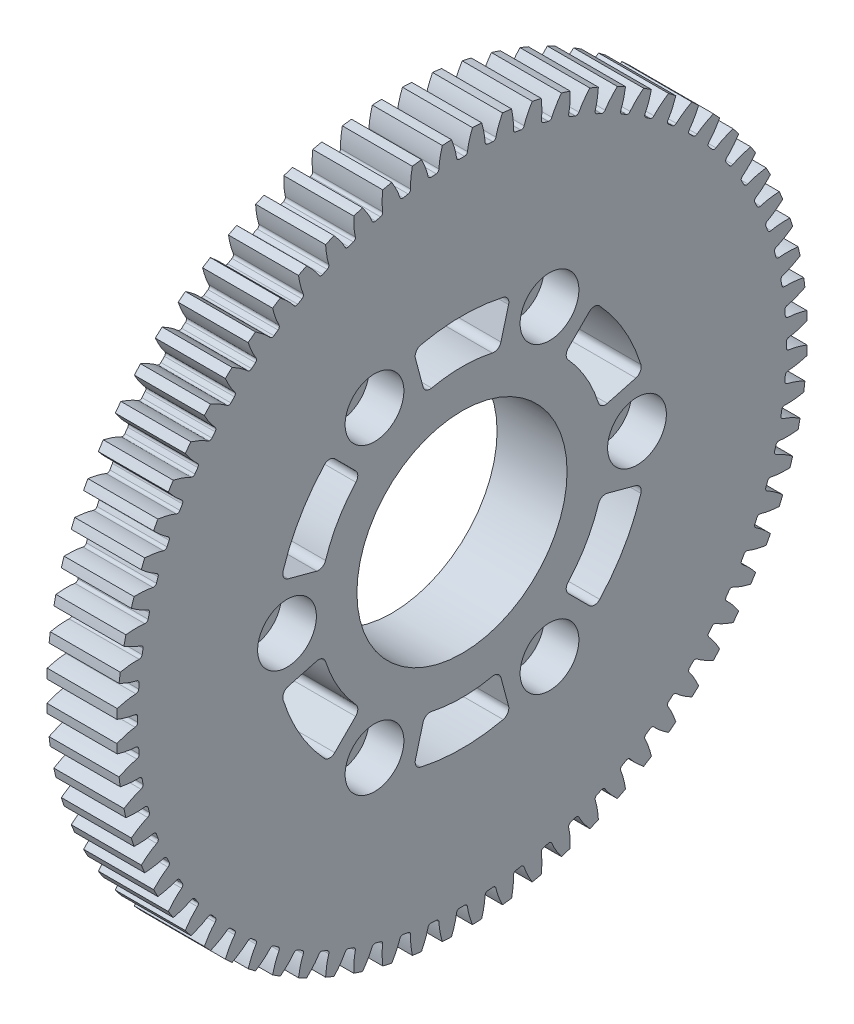
SolidWorks part; units mm, degrees
material "7075-T6 (SN)"
ref_plane "Front Plane" through (0, 0, 0) normal (0, 0, 1) x (1, 0, 0)
ref_plane "Top Plane" through (0, 0, 0) normal (0, 1, 0) x (1, 0, 0)
ref_plane "Right Plane" through (0, 0, 0) normal (1, 0, 0) x (0, 0, -1)
ref_axis "Axis1" through (-8.8445, 0, 0) along (1, 0, 0)
sketch "Sketch1" plane through (0, 0, 0) normal (1, 0, 0) x (0, 0, -1)
  circle A0 centre (0, 0) radius 46.99
  dimension "D1" = 93.98
extrude "Boss-Extrude1" add sketch "Sketch1" along normal mid plane 9.525
sketch "Sketch2" plane through (0, 0, 0) normal (1, 0, 0) x (0, 0, -1)
  line L0 (44.2579, 0.7202) -> (44.1267, 0.7181)
  line L1 (44.2579, -0.7202) -> (44.1267, -0.7181)
  circle A0 centre (0, 0) radius 46.99 construction
  circle A1 centre (0, 0) radius 45.72 construction
  circle A2 centre (0, 0) radius 44.2637 construction
  circle A3 centre (0, 0) radius 44.1325 construction
  circle A4 centre (0, 0) radius 46.99 construction
  arc A5 (44.1267, 0.7181) -> (44.1267, -0.7181) centre (0, 0) cw
  arc A6 (46.9684, 1.4236) -> (46.9684, -1.4236) centre (0, 0) cw
  spline S0 degree 4 poles (44.2579, 0.7202) (44.262, 0.7203) (44.2737, 0.7207) (44.2957, 0.7218) (44.3316, 0.7241) (44.3774, 0.7279) (44.4367, 0.7337) (44.5065, 0.7417) (44.5833, 0.7517) (44.667, 0.764) (44.7505, 0.7774) (44.8338, 0.792) (44.917, 0.8074) (45.0177, 0.8274) (45.1387, 0.853) (45.2803, 0.8853) (45.4412, 0.9248) (45.6054, 0.9682) (45.7673, 1.0134) (45.9313, 1.062) (46.0901, 1.1111) (46.2555, 1.1652) (46.4084, 1.2166) (46.5801, 1.2776) (46.7189, 1.3278) (46.9024, 1.3977) (47.0109, 1.44) (47.1382, 1.4908) (47.1948, 1.514) (47.2297, 1.5283) knots 0 0 0 0 0 0.005377 0.015084 0.028532 0.04661 0.064855 0.092111 0.119476 0.146842 0.174209 0.201575 0.228941 0.256307 0.307035 0.361767 0.4165 0.471232 0.525964 0.580697 0.635429 0.690161 0.744894 0.799626 0.854358 0.909091 0.954545 1 1 1 1 1 construction
  spline S1 degree 4 poles (44.2579, 0.7202) (44.262, 0.7203) (44.2737, 0.7207) (44.2957, 0.7218) (44.3316, 0.7241) (44.3774, 0.7279) (44.4367, 0.7337) (44.5065, 0.7417) (44.5833, 0.7517) (44.667, 0.764) (44.7505, 0.7774) (44.8338, 0.792) (44.917, 0.8074) (45.0177, 0.8274) (45.1387, 0.853) (45.2803, 0.8853) (45.4412, 0.9248) (45.6054, 0.9682) (45.7673, 1.0134) (45.9313, 1.062) (46.0901, 1.1111) (46.2555, 1.1652) (46.4084, 1.2166) (46.5801, 1.2776) (46.7189, 1.3278) (46.8626, 1.3825) (46.9326, 1.4096) (46.9684, 1.4236) knots 0 0 0 0 0 0.005377 0.015084 0.028532 0.04661 0.064855 0.092111 0.119476 0.146842 0.174209 0.201575 0.228941 0.256307 0.307035 0.361767 0.4165 0.471232 0.525964 0.580697 0.635429 0.690161 0.744894 0.799626 0.854358 0.909091 0.909091 0.909091 0.909091 0.909091
  spline S2 degree 4 poles (44.2579, -0.7202) (44.262, -0.7203) (44.2737, -0.7207) (44.2957, -0.7218) (44.3316, -0.7241) (44.3774, -0.7279) (44.4367, -0.7337) (44.5065, -0.7417) (44.5833, -0.7517) (44.667, -0.764) (44.7505, -0.7774) (44.8338, -0.792) (44.917, -0.8074) (45.0177, -0.8274) (45.1387, -0.853) (45.2803, -0.8853) (45.4412, -0.9248) (45.6054, -0.9682) (45.7673, -1.0134) (45.9313, -1.062) (46.0901, -1.1111) (46.2555, -1.1652) (46.4084, -1.2166) (46.5801, -1.2776) (46.7189, -1.3278) (46.9024, -1.3977) (47.0109, -1.44) (47.1382, -1.4908) (47.1948, -1.514) (47.2297, -1.5283) knots 0 0 0 0 0 0.005377 0.015084 0.028532 0.04661 0.064855 0.092111 0.119476 0.146842 0.174209 0.201575 0.228941 0.256307 0.307035 0.361767 0.4165 0.471232 0.525964 0.580697 0.635429 0.690161 0.744894 0.799626 0.854358 0.909091 0.954545 1 1 1 1 1 construction
  spline S3 degree 4 poles (44.2579, -0.7202) (44.262, -0.7203) (44.2737, -0.7207) (44.2957, -0.7218) (44.3316, -0.7241) (44.3774, -0.7279) (44.4367, -0.7337) (44.5065, -0.7417) (44.5833, -0.7517) (44.667, -0.764) (44.7505, -0.7774) (44.8338, -0.792) (44.917, -0.8074) (45.0177, -0.8274) (45.1387, -0.853) (45.2803, -0.8853) (45.4412, -0.9248) (45.6054, -0.9682) (45.7673, -1.0134) (45.9313, -1.062) (46.0901, -1.1111) (46.2555, -1.1652) (46.4084, -1.2166) (46.5801, -1.2776) (46.7189, -1.3278) (46.8626, -1.3825) (46.9326, -1.4096) (46.9684, -1.4236) knots 0 0 0 0 0 0.005377 0.015084 0.028532 0.04661 0.064855 0.092111 0.119476 0.146842 0.174209 0.201575 0.228941 0.256307 0.307035 0.361767 0.4165 0.471232 0.525964 0.580697 0.635429 0.690161 0.744894 0.799626 0.854358 0.909091 0.909091 0.909091 0.909091 0.909091
  dimension "D1" = 93.98
  dimension "D2" = 91.44
  dimension "D3" = 88.5274
  dimension "D4" = 88.265
extrude "Cut-Extrude1" cut sketch "Sketch2" against normal through all both and the other way through all
fillet "Fillet1" radius 0.397 2 edges at (0, -0.7181, -44.1267) (0, 0.7181, -44.1267)
pattern_circular "CirPattern1" count 72 over 360 about axis through (4.7625, 0, 0) along (-1, 0, 0) of "Cut-Extrude1", "Fillet1" reverse direction yes
sketch "Sketch5" [suppressed] plane through (0, 0, 0) normal (1, 0, 0) x (0, 0, -1)
  circle A0 centre (0, 0) radius 51.641 construction
  circle A1 centre (0, 0) radius 51.7525 construction
  circle A2 centre (0, 0) radius 53.34 construction
  circle A3 centre (0, 0) radius 54.61 construction
  arc A4 (51.6365, 0.6793) -> (51.6365, -0.6793) centre (0, 0) cw
  arc A5 (54.5918, 1.4103) -> (54.5918, -1.4103) centre (0, 0) cw
  spline S0 degree 4 poles (51.6365, 0.6793) (51.641, 0.6794) (51.6537, 0.6798) (51.6776, 0.6809) (51.7167, 0.6832) (51.7665, 0.687) (51.831, 0.6929) (51.9069, 0.7011) (51.9905, 0.7115) (52.0815, 0.7241) (52.1723, 0.738) (52.2631, 0.753) (52.3536, 0.769) (52.4633, 0.7897) (52.5951, 0.8162) (52.7493, 0.8497) (52.9246, 0.8907) (53.1037, 0.9358) (53.2802, 0.9828) (53.459, 1.0334) (53.6324, 1.0846) (53.8129, 1.1409) (53.9798, 1.1945) (54.1674, 1.2581) (54.319, 1.3104) (54.5196, 1.3833) (54.6383, 1.4275) (54.7774, 1.4805) (54.8393, 1.5048) (54.8775, 1.5197) knots 0 0 0 0 0 0.005377 0.015084 0.028532 0.04661 0.064855 0.092111 0.119476 0.146842 0.174209 0.201575 0.228941 0.256307 0.307035 0.361767 0.4165 0.471232 0.525964 0.580697 0.635429 0.690161 0.744894 0.799626 0.854358 0.909091 0.954545 1 1 1 1 1 construction
  spline S1 degree 4 poles (51.6365, 0.6793) (51.641, 0.6794) (51.6537, 0.6798) (51.6776, 0.6809) (51.7167, 0.6832) (51.7665, 0.687) (51.831, 0.6929) (51.9069, 0.7011) (51.9905, 0.7115) (52.0815, 0.7241) (52.1723, 0.738) (52.2631, 0.753) (52.3536, 0.769) (52.4633, 0.7897) (52.5951, 0.8162) (52.7493, 0.8497) (52.9246, 0.8907) (53.1037, 0.9358) (53.2802, 0.9828) (53.459, 1.0334) (53.6324, 1.0846) (53.8129, 1.1409) (53.9798, 1.1945) (54.1674, 1.2581) (54.319, 1.3104) (54.4761, 1.3675) (54.5526, 1.3957) (54.5918, 1.4103) knots 0 0 0 0 0 0.005377 0.015084 0.028532 0.04661 0.064855 0.092111 0.119476 0.146842 0.174209 0.201575 0.228941 0.256307 0.307035 0.361767 0.4165 0.471232 0.525964 0.580697 0.635429 0.690161 0.744894 0.799626 0.854358 0.909091 0.909091 0.909091 0.909091 0.909091
  spline S2 degree 4 poles (51.6365, -0.6793) (51.641, -0.6794) (51.6537, -0.6798) (51.6776, -0.6809) (51.7167, -0.6832) (51.7665, -0.687) (51.831, -0.6929) (51.9069, -0.7011) (51.9905, -0.7115) (52.0815, -0.7241) (52.1723, -0.738) (52.2631, -0.753) (52.3536, -0.769) (52.4633, -0.7897) (52.5951, -0.8162) (52.7493, -0.8497) (52.9246, -0.8907) (53.1037, -0.9358) (53.2802, -0.9828) (53.459, -1.0334) (53.6324, -1.0846) (53.8129, -1.1409) (53.9798, -1.1945) (54.1674, -1.2581) (54.319, -1.3104) (54.5196, -1.3833) (54.6383, -1.4275) (54.7774, -1.4805) (54.8393, -1.5048) (54.8775, -1.5197) knots 0 0 0 0 0 0.005377 0.015084 0.028532 0.04661 0.064855 0.092111 0.119476 0.146842 0.174209 0.201575 0.228941 0.256307 0.307035 0.361767 0.4165 0.471232 0.525964 0.580697 0.635429 0.690161 0.744894 0.799626 0.854358 0.909091 0.954545 1 1 1 1 1 construction
  spline S3 degree 4 poles (51.6365, -0.6793) (51.641, -0.6794) (51.6537, -0.6798) (51.6776, -0.6809) (51.7167, -0.6832) (51.7665, -0.687) (51.831, -0.6929) (51.9069, -0.7011) (51.9905, -0.7115) (52.0815, -0.7241) (52.1723, -0.738) (52.2631, -0.753) (52.3536, -0.769) (52.4633, -0.7897) (52.5951, -0.8162) (52.7493, -0.8497) (52.9246, -0.8907) (53.1037, -0.9358) (53.2802, -0.9828) (53.459, -1.0334) (53.6324, -1.0846) (53.8129, -1.1409) (53.9798, -1.1945) (54.1674, -1.2581) (54.319, -1.3104) (54.4761, -1.3675) (54.5526, -1.3957) (54.5918, -1.4103) knots 0 0 0 0 0 0.005377 0.015084 0.028532 0.04661 0.064855 0.092111 0.119476 0.146842 0.174209 0.201575 0.228941 0.256307 0.307035 0.361767 0.4165 0.471232 0.525964 0.580697 0.635429 0.690161 0.744894 0.799626 0.854358 0.909091 0.909091 0.909091 0.909091 0.909091
  dimension "D1" = 88.265
  dimension "D2" = 88.5274
  dimension "D3" = 91.44
  dimension "D4" = 93.98
extrude "Cut-Extrude2" [suppressed] cut sketch "Sketch5" against normal through all both and the other way through all
fillet "Fillet2" [suppressed] radius 0.397
pattern_circular "CirPattern2" [suppressed] count 84 over 360 of bodies 108
sketch "Sketch6" plane through (0, 0, 0) normal (1, 0, 0) x (0, 0, -1)
  line L0 (-6.5999, 24.6311) -> (-5.047, 18.8356)
  line L1 (23.8125, 0) -> (11.9062, 20.6222) construction
  line L2 (11.9062, 20.6222) -> (-11.9063, 20.6222) construction
  line L3 (-11.9063, 20.6222) -> (-23.8125, 0) construction
  line L4 (-23.8125, 0) -> (-11.9063, -20.6222) construction
  line L5 (-11.9063, -20.6222) -> (11.9062, -20.6222) construction
  line L6 (11.9062, -20.6222) -> (23.8125, 0) construction
  line L7 (5.047, 18.8356) -> (6.5999, 24.6311)
  line L8 (0, 19.5) -> (0, 25.5) construction
  line L9 (18.0312, 18.0312) -> (13.7886, 13.7886)
  line L10 (18.8356, 5.047) -> (24.6311, 6.5999)
  line L11 (24.6311, -6.5999) -> (18.8356, -5.047)
  line L12 (13.7886, -13.7886) -> (18.0312, -18.0312)
  line L13 (6.5999, -24.6311) -> (5.047, -18.8356)
  line L14 (-5.047, -18.8356) -> (-6.5999, -24.6311)
  line L15 (-18.0312, -18.0312) -> (-13.7886, -13.7886)
  line L16 (-18.8356, -5.047) -> (-24.6311, -6.5999)
  line L17 (-24.6311, 6.5999) -> (-18.8356, 5.047)
  line L18 (-13.7886, 13.7886) -> (-18.0312, 18.0312)
  circle A0 centre (0, 0) radius 23.8125 construction
  circle A1 centre (-11.9063, 20.6222) radius 2.1463
  circle A2 centre (11.9062, 20.6222) radius 2.1463
  circle A3 centre (23.8125, 0) radius 2.1463
  circle A4 centre (11.9062, -20.6222) radius 2.1463
  circle A5 centre (-11.9063, -20.6222) radius 2.1463
  circle A6 centre (-23.8125, 0) radius 2.1463
  arc A7 (-5.047, 18.8356) -> (5.047, 18.8356) centre (0, 0) cw
  arc A8 (-6.5999, 24.6311) -> (6.5999, 24.6311) centre (0, 0) cw
  arc A9 (13.7886, 13.7886) -> (18.8356, 5.047) centre (0, 0) cw
  arc A10 (18.0312, 18.0312) -> (24.6311, 6.5999) centre (0, 0) cw
  arc A11 (18.8356, -5.047) -> (13.7886, -13.7886) centre (0, 0) cw
  arc A12 (24.6311, -6.5999) -> (18.0312, -18.0312) centre (0, 0) cw
  arc A13 (5.047, -18.8356) -> (-5.047, -18.8356) centre (0, 0) cw
  arc A14 (6.5999, -24.6311) -> (-6.5999, -24.6311) centre (0, 0) cw
  arc A15 (-13.7886, -13.7886) -> (-18.8356, -5.047) centre (0, 0) cw
  arc A16 (-18.0312, -18.0312) -> (-24.6311, -6.5999) centre (0, 0) cw
  arc A17 (-18.8356, 5.047) -> (-13.7886, 13.7886) centre (0, 0) cw
  arc A18 (-24.6311, 6.5999) -> (-18.0312, 18.0312) centre (0, 0) cw
  point P43 (0, 0)
  dimension "D1" = 47.625
  dimension "D2" = 4.2926
  dimension "D3" = 30
  dimension "D4" = 19.5
  dimension "D5" = 25.5
extrude "Cut-Extrude3" cut sketch "Sketch6" against normal through all both and the other way through all
sketch "Sketch8" plane through (4.7625, 0, 0) normal (1, 0, 0) x (0, 0, -1)
  circle A0 centre (-11.9063, 20.6222) radius 4.0005
  circle A1 centre (11.9062, 20.6222) radius 4.0005
  circle A2 centre (23.8125, 0) radius 4.0005
  circle A3 centre (11.9062, -20.6222) radius 4.0005
  circle A4 centre (-11.9063, -20.6222) radius 4.0005
  circle A5 centre (-23.8125, 0) radius 4.0005
  dimension "D1" = 8.001
extrude "Cut-Extrude5" cut sketch "Sketch8" against normal blind 4.7625
fillet "Fillet3" radius 0.9906 24 edges at (0, 13.7886, 13.7886) (0, 5.047, 18.8356) (0, 6.5999, 24.6311) (0, 18.0312, 18.0312) (0, -5.047, 18.8356) (0, -13.7886, 13.7886) (0, -18.0312, 18.0312) (0, -6.5999, 24.6311) (0, -18.8356, 5.047) (0, -18.8356, -5.047) (0, -24.6311, -6.5999) (0, -24.6311, 6.5999) (0, 18.8356, -5.047) (0, 24.6311, 6.5999) (0, 24.6311, -6.5999) (0, 5.047, -18.8356) (0, 13.7886, -13.7886) (0, 18.0312, -18.0312) (0, 6.5999, -24.6311) (0, -13.7886, -13.7886) (0, -5.047, -18.8356) (0, -6.5999, -24.6311) (0, -18.0312, -18.0312) (0, 18.8356, 5.047)
sketch "Sketch7" plane through (0, 0, 0) normal (1, 0, 0) x (0, 0, -1)
  circle A0 centre (0, 0) radius 14.3002
  dimension "D1" = 28.6004
extrude "Cut-Extrude4" cut sketch "Sketch7" against normal through all both and the other way through all
equation "\"DP\"= 20"
equation "\"N\" = 72"
equation "\"PA\"= 14.5"
equation "\"Addendum\"= 1 / \"DP\""
equation "\"Dedendum\"= 1.25 / \"DP\""
equation "\"Clearance\"= .25 / \"DP\""
equation "\"PitchCircle\"= \"N\" / \"DP\""
equation "\"OutsideDiameter\"= ( \"N\" + 2 ) / \"DP\""
equation "\"Fillet\"= \"Clearance\" * cos ( \"PA\" ) * tan ( ( 90 + \"PA\" ) / 2 )"
equation "\"AddendumCircle\"= \"PitchCircle\" + ( 2 * \"Addendum\" )"
equation "\"DedendumCircle\"= \"PitchCircle\" - ( 2 * \"Dedendum\" )"
equation "\"BaseCircle\"= \"PitchCircle\" * cos ( \"PA\" )"
equation "\"Alpha\"= SQR ( \"PitchCircle\" ^ 2 - \"BaseCircle\" ^ 2 ) / \"BaseCircle\" * 180 / PI - \"PA\""
equation "\"Beta\"= ( \"PitchAngle\" / 4 - \"Alpha\" )"
equation "\"Phi\"= SQR ( ( \"AddendumCircle\" / 2 ) ^ 2 - ( \"BaseCircle\" / 2 ) ^ 2 ) / ( \"BaseCircle\" / 2 )"
equation "\"D1@Sketch1\"=\"OutsideDiameter\""
equation "\"D1@Sketch2\"=\"OutsideDiameter\""
equation "\"D2@Sketch2\"=\"PitchCircle\""
equation "\"D3@Sketch2\"=\"BaseCircle\""
equation "\"D4@Sketch2\"=\"DedendumCircle\""
equation "\"D1@Fillet1\"=\"Fillet\""
equation "\"D1@CirPattern1\"=\"N\""
equation "\"D1@Sketch5\"=\"DedendumCircle\""
equation "\"D2@Sketch5\"=\"BaseCircle\""
equation "\"D3@Sketch5\"=\"PitchCircle\""
equation "\"D4@Sketch5\"=\"OutsideDiameter\""
equation "\"D1@Fillet2\"=\"Fillet\""
equation "\"PitchAngle\"= 360 / \"N\""
